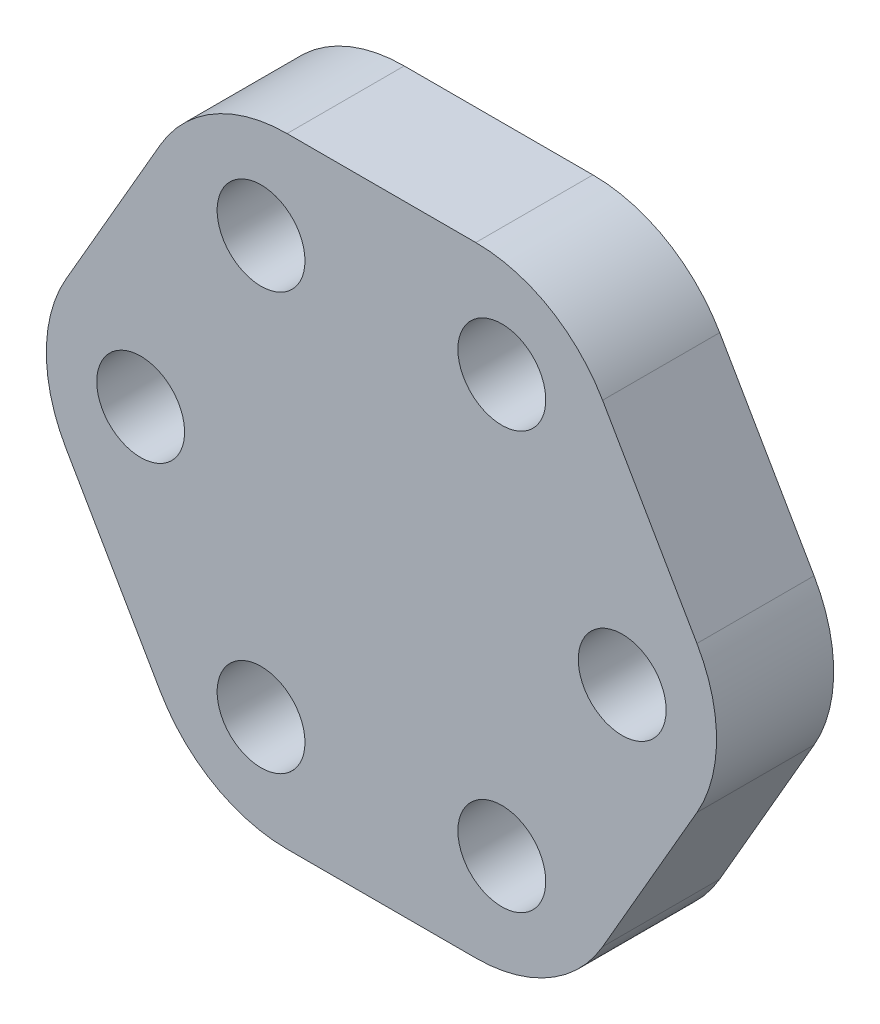
SolidWorks part; units mm, degrees
ref_plane "Front" through (0, 0, 0) normal (0, 0, 1) x (1, 0, 0)
ref_plane "Top" through (0, 0, 0) normal (0, 1, 0) x (1, 0, 0)
ref_plane "Right" through (0, 0, 0) normal (1, 0, 0) x (0, 0, -1)
sketch "Sketch1" plane through (0, 0, 0) normal (0, 0, 1) x (1, 0, 0)
  line L1 (6.1091, -10.5813) -> (12.2182, 0)
  line L2 (12.2182, 0) -> (6.1091, 10.5813)
  line L3 (6.1091, 10.5813) -> (-6.1091, 10.5813)
  line L4 (-6.1091, 10.5813) -> (-12.2182, 0)
  line L5 (-12.2182, 0) -> (-6.1091, -10.5813)
  line L6 (-6.1091, -10.5813) -> (6.1091, -10.5813)
  circle A0 centre (0, 0) radius 10.5813 construction
  circle A1 centre (0, 0) radius 5 construction
  circle A2 centre (-4.175, 7.2313) radius 3.35 construction
  dimension "D1" = 10
  dimension "D2" = 6.7
extrude "Boss-Extrude1" add sketch "Sketch1" along normal blind 4
fillet "Fillet1" radius 5 6 edges at (6.1091, -10.5813, 2) (-6.1091, -10.5813, 2) (-12.2182, 0, 2) (12.2182, 0, 2) (6.1091, 10.5813, 2) (-6.1091, 10.5813, 2)
sketch "Sketch2" plane through (0, 0, 4) normal (0, 0, 1) x (1, 0, 0)
  line L0 (-5.7224, -9.9114) -> (-4.1112, -7.1208) construction
  line L1 (-4.1112, -7.1208) -> (-2.5, -4.3301) construction
  line L2 (-2.5, -4.3301) -> (0, 0) construction
  circle A0 centre (0, 0) radius 5 construction
  arc A1 (-7.5525, -8.0813) -> (-3.2224, -10.5813) centre (-3.2224, -5.5813) ccw construction
  circle A2 centre (0, 0) radius 5 construction
  circle A3 centre (-4.1112, -7.1208) radius 1.5
  dimension "D1" = 3
extrude "Cut-Extrude1" cut sketch "Sketch2" against normal through all
ref_axis "Axis1" through (0, 0, -80.9) along (0, 0, 1)
pattern_circular "CirPattern1" count 6 over 360 about axis through (0, 0, -80.9) along (0, 0, 1) of "Cut-Extrude1"
